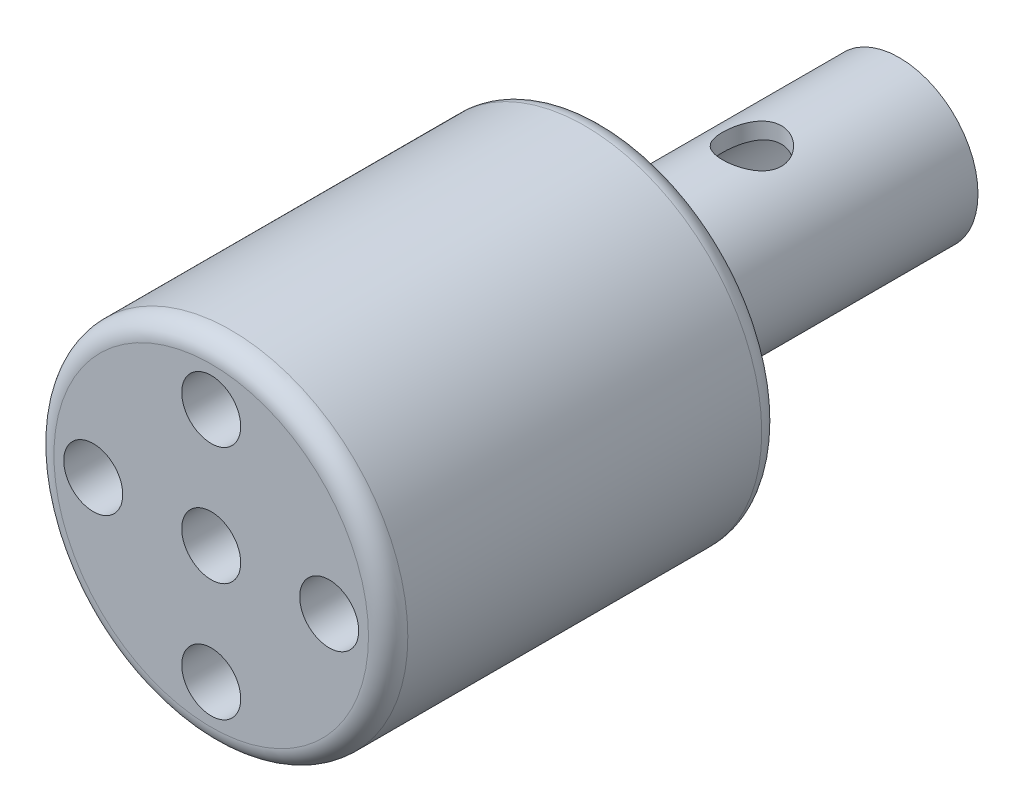
SolidWorks part; units mm, degrees
ref_plane "Plan de face" through (0, 0, 0) normal (0, 0, 1) x (1, 0, 0)
ref_plane "Plan de dessus" through (0, 0, 0) normal (0, 1, 0) x (1, 0, 0)
ref_plane "Plan de droite" through (0, 0, 0) normal (1, 0, 0) x (0, 0, -1)
sketch "Esquisse1" plane through (0, 0, 0) normal (0, 0, 1) x (1, 0, 0)
  line L0 (0, 0) -> (0, 6) construction
  circle A0 centre (0, 0) radius 9
  circle A1 centre (0, 6) radius 1.5
  circle A2 centre (0, 0) radius 6 construction
  circle A3 centre (6, 0) radius 1.5
  circle A4 centre (0, -6) radius 1.5
  circle A5 centre (-6, 0) radius 1.5
  point P15 (0, 0)
  dimension "D1" = 18
  dimension "D3" = 3
  dimension "D2" = 6
  dimension "D4" = 4
extrude "Boss.-Extru.1" add sketch "Esquisse1" along normal blind 20
sketch "Esquisse2" plane through (0, 0, 0) normal (0, 0, -1) x (-1, 0, 0)
  circle A0 centre (0, 0) radius 4
  circle A1 centre (0, 0) radius 3.19
  dimension "D1" = 8
  dimension "D2" = 6.38
extrude "Boss.-Extru.2" add sketch "Esquisse2" along normal blind 15
fillet "Congé1" radius 0.25 1 edges at (4, 0, 0)
fillet "Congé2" radius 1 1 edges at (9, 0, 20)
fillet "Congé3" radius 1 1 edges at (9, 0, 0)
sketch "Esquisse3" plane through (0, 0, 0) normal (0, 1, 0) x (1, 0, 0)
  line L0 (0, 15) -> (0, 0) construction
  line L1 (3.19, 15) -> (-3.19, 15) construction
  circle A0 centre (0, 7.5) radius 1.5
  dimension "D1" = 3
extrude "Enlèv. mat.-Extru.1" cut sketch "Esquisse3" against normal blind 10 and the other way blind 10
sketch "Esquisse4" plane through (0, 0, 20) normal (0, 0, 1) x (1, 0, 0)
  circle A0 centre (0, 0) radius 1.5
  dimension "D1" = 3
extrude "Enlèv. mat.-Extru.2" cut sketch "Esquisse4" against normal blind 10
